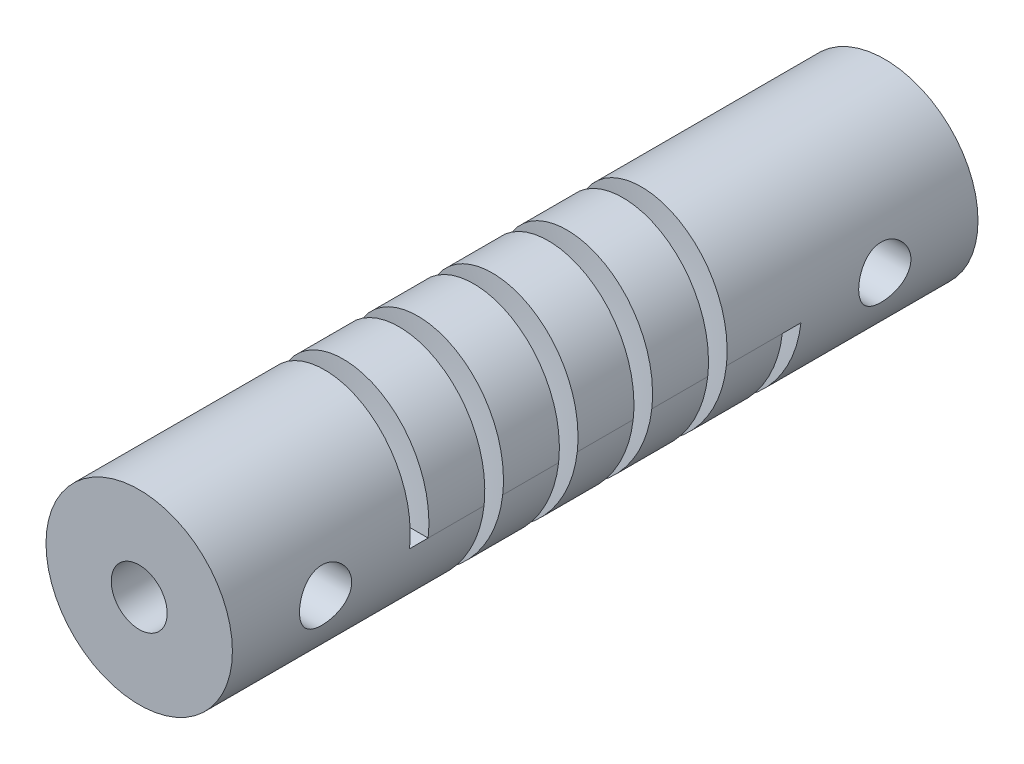
SolidWorks part; units mm, degrees
ref_plane "Alzado" through (0, 0, 0) normal (0, 0, 1) x (1, 0, 0)
ref_plane "Planta" through (0, 0, 0) normal (0, 1, 0) x (1, 0, 0)
ref_plane "Vista lateral" through (0, 0, 0) normal (1, 0, 0) x (0, 0, -1)
sketch "Croquis1" plane through (0, 0, 0) normal (0, 0, 1) x (1, 0, 0)
  circle A0 centre (0, 0) radius 5
  dimension "D1" = 10
extrude "Saliente-Extruir1" add sketch "Croquis1" along normal blind 40
sketch "Croquis2" plane through (0, 0, 40) normal (0, 0, 1) x (1, 0, 0)
  circle A0 centre (0, 0) radius 1.5
  dimension "D1" = 3
extrude "Cortar-Extruir1" cut sketch "Croquis2" against normal blind 20
sketch "Croquis3" plane through (0, 0, 0) normal (0, 0, -1) x (-1, 0, 0)
  circle A0 centre (0, 0) radius 2
  dimension "D1" = 4
extrude "Cortar-Extruir2" cut sketch "Croquis3" against normal blind 20
ref_plane "Plano1" through (0, 0, 10) normal (0, 0, 1) x (1, 0, 0)
sketch "Croquis5" plane through (0, 0, 10) normal (0, 0, 1) x (1, 0, 0)
  circle A0 centre (0, 0) radius 5
curve "Hélice/Espiral1" pitch 4 height 20 turns 5
sketch "Croquis6" plane through (0, 0, 0) normal (0, 1, 0) x (1, 0, 0)
  line L2 (5, -40) -> (5, 0) construction
  line L3 (5, -9.5) -> (1, -9.5)
  line L4 (1, -9.5) -> (1, -10.5)
  line L5 (1, -10.5) -> (6.2, -10.5)
  line L6 (6.2, -10.5) -> (6.2, -9.5)
  line L7 (6.2, -9.5) -> (5, -9.5)
  dimension "D1" = 5.2
  dimension "D2" = 4
sweep "Cortar-Barrer2" cut profiles "Croquis6" path "Hélice/Espiral1" align with end faces yes
sketch "Croquis7" plane through (0, 0, 0) normal (1, 0, 0) x (0, 0, -1)
  line L0 (-40, 5) -> (-40, -5) construction
  circle A0 centre (-5, 0) radius 1.4
  circle A1 centre (-35, 0) radius 1.4
  dimension "D3" = 2.8
  dimension "D4" = 2.8
  dimension "D1" = 5
  dimension "D2" = 5
extrude "Cortar-Extruir3" cut sketch "Croquis7" against normal through all both and the other way through all
